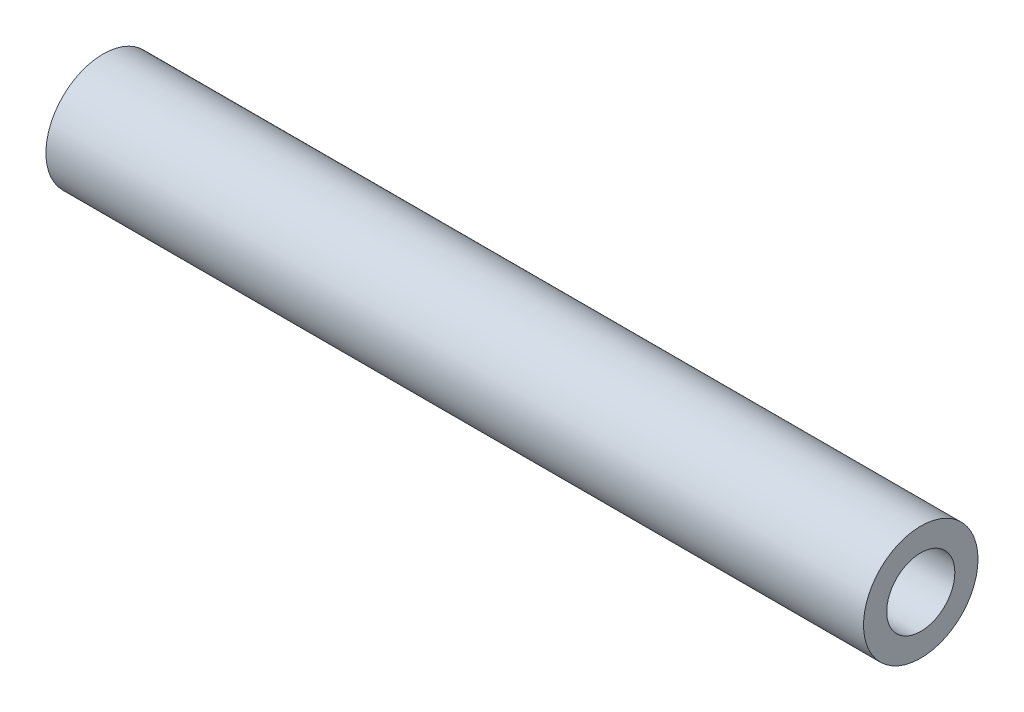
SolidWorks part; units mm, degrees
material "PVC 0.007 Plasticized"
ref_plane "Front Plane" through (0, 0, 0) normal (0, 0, 1) x (1, 0, 0)
ref_plane "Top Plane" through (0, 0, 0) normal (0, 1, 0) x (1, 0, 0)
ref_plane "Right Plane" through (0, 0, 0) normal (1, 0, 0) x (0, 0, -1)
sketch "Sketch1" plane through (0, 0, 0) normal (1, 0, 0) x (0, 0, -1)
  circle A0 centre (0, 0) radius 10.668
  circle A1 centre (0, 0) radius 6.35
  dimension "D1" = 21.336
  dimension "D2" = 12.7
extrude "Boss-Extrude1" add sketch "Sketch1" against normal blind 152.4
